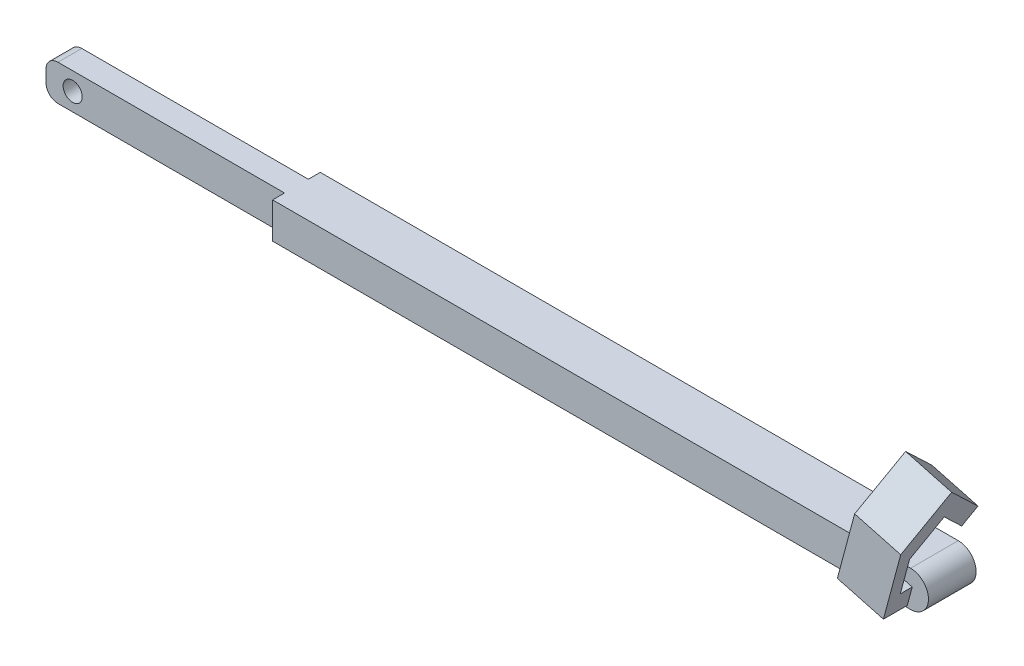
SolidWorks part; units mm, degrees
material "ABS"
ref_plane "Front Plane" through (0, 0, 0) normal (0, 0, 1) x (1, 0, 0)
ref_plane "Top Plane" through (0, 0, 0) normal (0, 1, 0) x (1, 0, 0)
ref_plane "Right Plane" through (0, 0, 0) normal (1, 0, 0) x (0, 0, -1)
sketch "Sketch1" plane through (0, 0, 0) normal (0, 0, 1) x (1, 0, 0)
  line L0 (-90, 0) -> (90, 0) construction
  line L1 (-90, 3.75) -> (90, 3.75)
  line L2 (-90, -3.75) -> (90, -3.75)
  arc A0 (-90, 3.75) -> (-90, -3.75) centre (-90, 0) ccw
  arc A1 (90, -3.75) -> (90, 3.75) centre (90, 0) ccw
  circle A2 centre (-90, 0) radius 2
  point P2 (0, 0)
  dimension "D3" = 4
  dimension "D1" = 180
  dimension "D2" = 7.5
extrude "Boss-Extrude1" add sketch "Sketch1" along normal blind 10
sketch "Sketch2" plane through (0, 0, 10) normal (0, 0, 1) x (1, 0, 0)
  line L0 (-35.0001, -0.1276) -> (49964.9999, -0.1276) construction
  line L1 (80.6879, 3.0983) -> (90.3472, 0.5101)
  line L2 (80.6879, 3.0983) -> (79.6526, -0.7654)
  line L3 (79.6526, -0.7654) -> (89.3119, -3.3536)
  line L4 (90.3472, 0.5101) -> (89.3119, -3.3536)
  line L5 (80.6879, 3.0983) -> (89.3119, -3.3536) construction
  line L6 (79.6526, -0.7654) -> (90.3472, 0.5101) construction
  point P0 (84.9999, -0.1276)
  dimension "D1" = 10
  dimension "D2" = 4
  dimension "D3" = 85
  dimension "D4" = 165
extrude "Boss-Extrude2" add sketch "Sketch2" along normal blind 5
sketch "Sketch3" plane through (6.1796, 23.0627, 0) normal (0.2588, 0.9659, 0) x (0.9659, -0.2588, 0)
  line L1 (77.1366, -15) -> (87.1366, -15)
  line L2 (77.1366, -15) -> (77.1366, -10)
  line L3 (77.1366, -10) -> (87.1366, -10)
  line L4 (87.1366, -15) -> (87.1366, -10)
sketch "Sketch11" plane through (6.1796, 23.0627, 0) normal (0.2588, 0.9659, 0) x (0.9659, -0.2588, 0)
  line L0 (87.1366, -15) -> (87.1366, -10) construction
  line L1 (77.1366, -15) -> (87.1366, -15)
  line L2 (77.1366, -15) -> (77.1366, -12.5)
  line L3 (77.1366, -12.5) -> (87.1366, -12.5)
  line L4 (87.1366, -15) -> (87.1366, -12.5)
  dimension "D1" = 2.5
extrude "Boss-Extrude9" add sketch "Sketch11" along normal blind 10
chamfer "Chamfer4" distance 2.5 angle 45 1 edges at (88.1057, 11.4635, 12.5)
sketch "Sketch12" plane through (2.4428, 9.1166, -9.4382) normal (0.183, 0.683, -0.7071) x (-0.9831, 0.1271, -0.1317)
  line L0 (-91.3907, 14.2511) -> (-81.5657, 16.1138)
  line L1 (-91.3907, 14.2511) -> (-92.0493, 17.7248)
  line L2 (-81.5657, 16.1138) -> (-82.2243, 19.5875)
  line L3 (-92.0493, 17.7248) -> (-82.2243, 19.5875)
  line L4 (-91.3907, 14.2511) -> (-90.4029, 9.0406) construction
  line L5 (-81.5657, 16.1138) -> (-91.3907, 14.2511) construction
extrude "Boss-Extrude10" add sketch "Sketch12" along normal blind 12
sketch "Sketch13" plane through (5.678, 21.1906, 21.9382) normal (-0.183, -0.683, -0.7071) x (-0.9831, 0.1271, 0.1317)
  line L0 (-90.3331, 8.6728) -> (-80.5082, 10.5355)
  line L1 (-90.3331, 8.6728) -> (-89.6178, 4.9)
  line L2 (-80.5082, 10.5355) -> (-79.7929, 6.7627)
  line L3 (-89.6178, 4.9) -> (-79.7929, 6.7627)
  line L4 (-80.5082, 10.5355) -> (-78.2729, -1.2545) construction
  dimension "D1" = 3.84
extrude "Boss-Extrude11" add sketch "Sketch13" along normal blind 7
sketch "Sketch14" plane through (0, 0, 10) normal (0, 0, 1) x (1, 0, 0)
  line L0 (-90, -3.75) -> (90, -3.75) construction
  line L1 (-81.3159, -3.75) -> (-43.75, -3.75)
  line L2 (-81.3159, -3.75) -> (-81.3159, 3.75)
  line L3 (-81.3159, 3.75) -> (-43.75, 3.75)
  line L4 (-43.75, -3.75) -> (-43.75, 3.75)
  line L5 (90, 3.75) -> (-90, 3.75) construction
  arc A0 (-90, 3.75) -> (-90, -3.75) centre (-90, 0) ccw construction
  point P11 (-93.75, 0)
  dimension "D1" = 50
extrude "Cut-Extrude2" cut sketch "Sketch14" against normal through all
sketch "Sketch15" plane through (-43.75, 0, 0) normal (-1, 0, 0) x (0, 0, 1)
  line L0 (0, -3.75) -> (10, -3.75) construction
  line L1 (2.5, -3.75) -> (7.5, -3.75)
  line L2 (2.5, -3.75) -> (2.5, 3.75)
  line L3 (2.5, 3.75) -> (7.5, 3.75)
  line L4 (7.5, -3.75) -> (7.5, 3.75)
  line L5 (0, 3.75) -> (10, 3.75) construction
  point P8 (5, 3.75)
  dimension "D1" = 5
extrude "Boss-Extrude12" add sketch "Sketch15" along normal blind 50
sketch "Sketch16" plane through (0, 0, 7.5) normal (0, 0, 1) x (1, 0, 0)
  circle A0 centre (-88.16, 0) radius 2
  dimension "D1" = 4
fillet "Fillet1" radius 2.5 1 edges at (-93.75, 3.75, 5)
fillet "Fillet2" radius 2.5 1 edges at (-93.75, -3.75, 5)
extrude "Cut-Extrude3" cut sketch "Sketch16" against normal blind 50 contours A0
